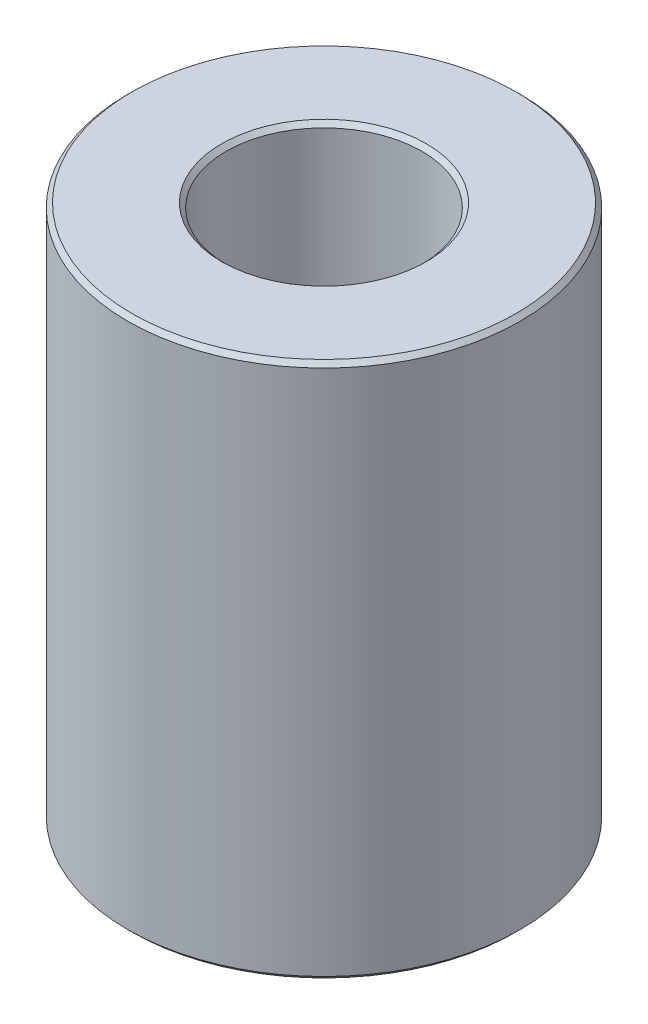
SolidWorks part; units mm, degrees
ref_plane "Front Plane" through (0, 0, 0) normal (0, 0, 1) x (1, 0, 0)
ref_plane "Top Plane" through (0, 0, 0) normal (0, 1, 0) x (1, 0, 0)
ref_plane "Right Plane" through (0, 0, 0) normal (1, 0, 0) x (0, 0, -1)
sketch "Sketch1" plane through (0, 0, 0) normal (0, 1, 0) x (1, 0, 0)
  circle A0 centre (0, 0) radius 35
  dimension "SLEEVE_OD" = 70
extrude "Boss-Extrude1" add sketch "Sketch1" along normal blind 95.4662
sketch "Sketch2" plane through (0, 0, 0) normal (0, 1, 0) x (1, 0, 0)
  circle A0 centre (0, 0) radius 17.4447
  dimension "BORE_D" = 34.8894
extrude "Cut-Extrude1" cut sketch "Sketch2" along normal through all
chamfer "Chamfer1" distance 0.7813 angle 45 4 edges at (0, 95.4662, 17.4447) (0, 0, 17.4447) (0, 0, 35) (0, 95.4662, 35)
